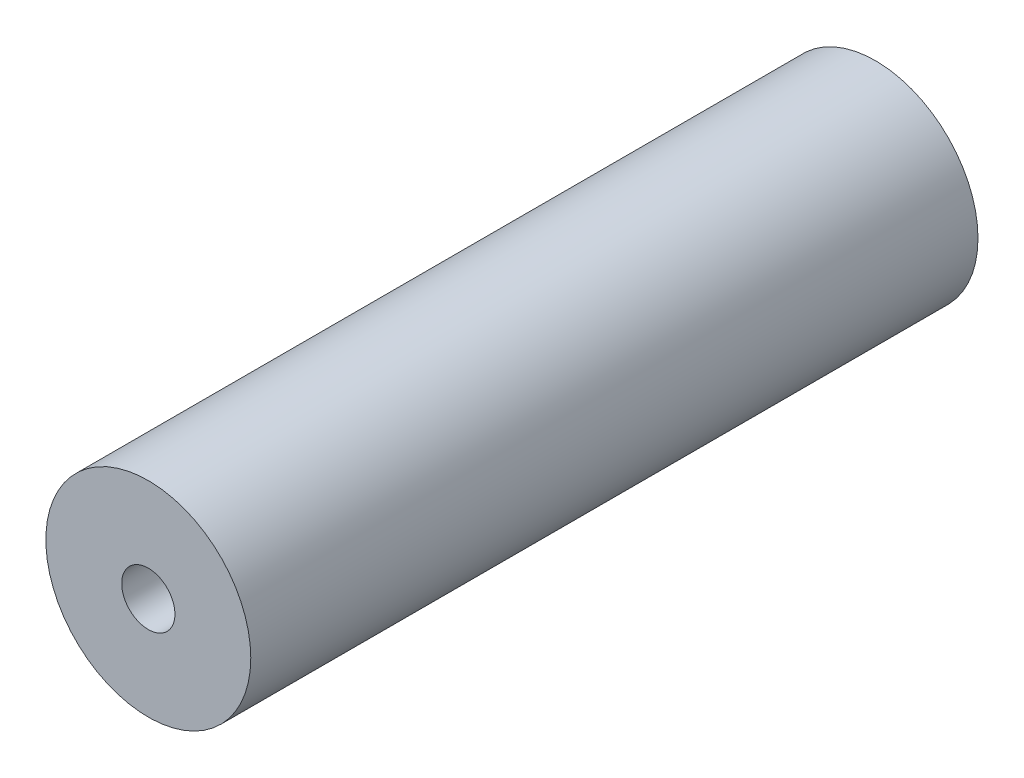
SolidWorks part; units mm, degrees
ref_plane "Ebene vorne" through (0, 0, 0) normal (0, 0, 1) x (1, 0, 0)
ref_plane "Ebene oben" through (0, 0, 0) normal (0, 1, 0) x (1, 0, 0)
ref_plane "Ebene rechts" through (0, 0, 0) normal (1, 0, 0) x (0, 0, -1)
sketch "Skizze1" plane through (0, 0, 0) normal (0, 0, 1) x (1, 0, 0)
  circle A0 centre (0, 0) radius 15.5
  circle A1 centre (0, 0) radius 4.025
  dimension "D1" = 31
  dimension "D2" = 8.05
extrude "Aufsatz-Linear austragen1" add sketch "Skizze1" along normal blind 110
ref_axis "Achse1" through (0, 0, 110) along (0, 0, -1)
